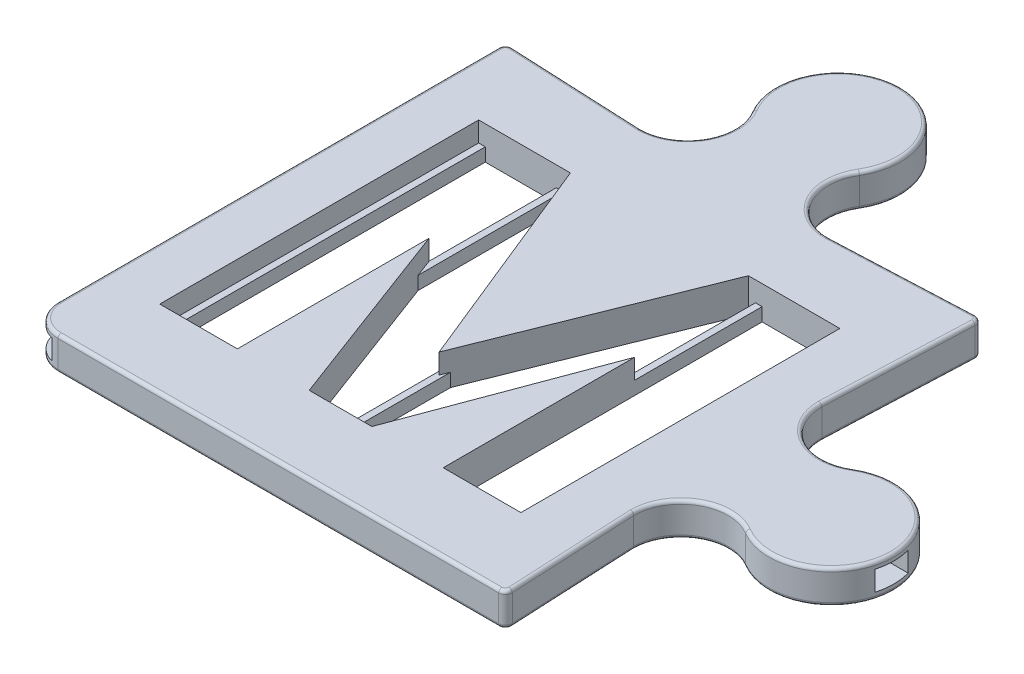
SolidWorks part; units mm, degrees
ref_plane "Front Plane" through (0, 0, 0) normal (0, 0, 1) x (1, 0, 0)
ref_plane "Top Plane" through (0, 0, 0) normal (0, 1, 0) x (1, 0, 0)
ref_plane "Right Plane" through (0, 0, 0) normal (1, 0, 0) x (0, 0, -1)
sketch "Sketch1" plane through (0, 0, 0) normal (0, 1, 0) x (1, 0, 0)
  line L0 (-31, -36) -> (37, -36) construction
  line L1 (-36, 37) -> (-36, -31) construction
  line L2 (-14.1421, 36) -> (-36, 37) construction
  line L3 (37, 37) -> (14.1421, 36) construction
  line L4 (36, 13.1421) -> (37, 37) construction
  line L5 (37, -36) -> (36, -15.1421) construction
  line L6 (-35.4, 36.3719) -> (-35.4, -31)
  line L7 (-36, 36) -> (36, 36) construction
  line L8 (-36, 36) -> (-36, -36) construction
  line L9 (-36, -36) -> (36, -36) construction
  line L10 (36, 36) -> (36, -36) construction
  line L11 (-31, -35.4) -> (36.3705, -35.4)
  line L12 (36.3705, -35.4) -> (35.4, -15.1568)
  line L13 (35.4, 13.155) -> (36.3732, 36.372)
  line L14 (36.3732, 36.372) -> (14.1555, 35.4)
  line L15 (-14.1562, 35.4) -> (-35.4, 36.3719)
  line L16 (-30, -24) -> (30, -24) construction
  line L17 (-30, 29) -> (30, 29) construction
  line L18 (-30, 29) -> (-30, -31) construction
  line L19 (-30, -31) -> (30, -31) construction
  line L20 (30, 29) -> (30, -31) construction
  line L21 (-30, 24) -> (30, 24) construction
  line L22 (-30, 24) -> (-30, -26) construction
  line L23 (-30, -26) -> (30, -26) construction
  line L24 (30, 24) -> (30, -26) construction
  arc A0 (-36, -31) -> (-31, -36) centre (-31, -31) ccw construction
  arc A1 (-14.1421, 36) -> (-8.571, 45.8485) centre (-14.1421, 42.5) ccw construction
  arc A2 (8.571, 45.8485) -> (-8.571, 45.8485) centre (0, 51) ccw construction
  arc A3 (8.571, 45.8485) -> (14.1421, 36) centre (14.1421, 42.5) ccw construction
  arc A4 (36, 13.1421) -> (45.8485, 7.571) centre (42.5, 13.1421) ccw construction
  arc A5 (45.8485, -9.571) -> (45.8485, 7.571) centre (51, -1) ccw construction
  arc A6 (45.8485, -9.571) -> (36, -15.1421) centre (42.5, -15.1421) ccw construction
  arc A7 (-35.4, -31) -> (-31, -35.4) centre (-31, -31) ccw
  arc A8 (46.1576, -9.0567) -> (35.4, -15.1568) centre (42.5, -15.1421) ccw
  arc A9 (46.1576, -9.0567) -> (46.1576, 7.0567) centre (51, -1) ccw
  arc A10 (35.4, 13.155) -> (46.1576, 7.0567) centre (42.5, 13.1421) ccw
  arc A11 (8.0567, 46.1576) -> (14.1555, 35.4) centre (14.1421, 42.5) ccw
  arc A12 (8.0567, 46.1576) -> (-8.0567, 46.1576) centre (0, 51) ccw
  arc A13 (-14.1562, 35.4) -> (-8.0567, 46.1576) centre (-14.1421, 42.5) ccw
  point P32 (36, 0)
  point P34 (0, 36)
  dimension "D5" = 6.5
  dimension "D6" = 10
  dimension "D7" = 6.5
  dimension "D13" = 5
  dimension "D9" = 10
  dimension "D11" = 6.5
  dimension "D12" = 6.5
  dimension "D1" = 72
  dimension "D2" = 1
  dimension "D3" = 1
  dimension "D4" = 15
  dimension "D8" = 1
  dimension "D10" = 35
  dimension "D14" = 15
  dimension "D15" = 36
  dimension "D16" = 1
  dimension "D18" = 60
  dimension "D19" = 60
  dimension "D20" = 5
  dimension "D21" = 6
  dimension "D22" = 5
  dimension "D23" = 50
  dimension "D24" = 2
  dimension "D17" = 0.6
extrude "Boss-Extrude1" add sketch "Sketch1" along normal blind 5
sketch "Sketch6" plane through (0, 0, 0) normal (0, -1, 0) x (1, 0, 0)
  line L0 (-35.4, -36.3719) -> (-35.4, 31) construction
  line L1 (-35.4, 17.9) -> (-27.4, 17.9)
  line L2 (-35.4, 17.9) -> (-35.4, -16.1)
  line L3 (-35.4, -16.1) -> (-27.4, -16.1)
  line L4 (-27.4, 17.9) -> (-27.4, -16.1)
  line L5 (-31, 35.4) -> (36.3705, 35.4) construction
  line L6 (-35.4, 14.65) -> (-30.4, 14.65)
  line L7 (-35.4, 14.65) -> (-35.4, -12.85)
  line L8 (-35.4, -12.85) -> (-30.4, -12.85)
  line L9 (-30.4, 14.65) -> (-30.4, -12.85)
  point P15 (-27.4, 0.9)
  point P16 (-30.4, 0.9)
  line M28 (-35.4, 31) -> (-35.4, -36.3719)
  dimension "D1" = 8
  dimension "D2" = 20.75
  dimension "D3" = 27.5
  dimension "D4" = 5
  dimension "D5" = 34
extrude "Cut-Extrude3" cut sketch "Sketch6" against normal blind 3 from offset 1 contours L6 L9 L8 L3 L4 L1 M28 | L9 L6 L2 L8 region at (-29.8665, 0, 0.9) region at (-32.9, 0, 0.9) offset against normal yes
extrude "Cut-Extrude4" cut sketch "Sketch6<3>" against normal up to next contours L9 L6 L2 L8 region at (-32.9, 0, 0.9)
sketch "Sketch6<3>" plane through (0, 0, 0) normal (0, -1, 0) x (1, 0, 0) same geometry as "Sketch6"
sketch "Sketch8" plane through (0, 0, 0) normal (0, -1, 0) x (1, 0, 0)
  line L1 (-2.5, -51.4) -> (2.5, -51.4)
  line L2 (-2.5, -51.4) -> (-2.5, -60.4)
  line L3 (-2.5, -60.4) -> (2.5, -60.4)
  line L4 (2.5, -51.4) -> (2.5, -60.4)
  line L5 (51.4, 3.5) -> (60.4, 3.5)
  line L6 (51.4, 3.5) -> (51.4, -1.5)
  line L7 (51.4, -1.5) -> (60.4, -1.5)
  line L8 (60.4, 3.5) -> (60.4, -1.5)
  arc A0 (-8.0567, -46.1576) -> (8.0567, -46.1576) centre (0, -51) ccw construction
  arc A1 (46.1576, -7.0567) -> (46.1576, 9.0567) centre (51, 1) ccw construction
  point P4 (0, -60.4)
  point P13 (60.4, 1)
  dimension "D1" = 5
  dimension "D2" = 9
  dimension "D3" = 5
  dimension "D4" = 9
extrude "Cut-Extrude5" cut sketch "Sketch8" against normal blind 3 from offset 1 offset against normal yes
sketch "Sketch9" plane through (0, 0, 0) normal (0, -1, 0) x (1, 0, 0)
  line L0 (-31, 35.4) -> (36.3705, 35.4) construction
  line L1 (-35.4, 14.65) -> (-35.4, 31) construction
  line L2 (-31.7636, 35.3332) -> (-35.4, 31) construction
  line L3 (-33.2571, 29.735) -> (-30.0429, 33.565) construction
  line L4 (-30.0429, 33.565) -> (-33.2571, 29.735) construction
  line L5 (-30.0429, 33.565) -> (-32.7119, 35.8048)
  line L6 (-33.2571, 29.735) -> (-35.926, 31.9747)
  line L7 (-32.7119, 35.8048) -> (-35.926, 31.9747)
  circle A0 centre (-31.65, 31.65) radius 2.5
  arc A1 (-31, 35.4) -> (-35.4, 31) centre (-31, 31) ccw construction
  arc M41 (-31, 35.4) -> (-35.4, 31) centre (-31, 31) ccw
  dimension "D1" = 5
  dimension "D3" = 3.75
  dimension "D4" = 5.6569
  dimension "D2" = 3.75
extrude "Cut-Extrude6" cut sketch "Sketch9" against normal blind 3 from offset 1 contours A0 L5 L6 M41 | A0 L5 region at (-33.6239, 0, 33.3064) region at (-31.65, 0, 31.65) offset against normal yes
sketch "Sketch11" plane through (-35.4, 0, 0) normal (-1, 0, 0) x (0, 0, 1)
  line L0 (-13.155, 0) -> (-36.372, 0) construction
  line L1 (-25.1, 3) -> (-19.1, 3)
  line L2 (-25.1, 3) -> (-25.1, 1.5)
  line L3 (-25.1, 1.5) -> (-19.1, 1.5)
  line L4 (-19.1, 3) -> (-19.1, 1.5)
  line L5 (-16.1, 4) -> (-16.1, 1) construction
  line L6 (35.4, 0) -> (15.1568, 0) construction
  line L7 (20.9, 3) -> (26.9, 3)
  line L8 (20.9, 3) -> (20.9, 1.5)
  line L9 (20.9, 1.5) -> (26.9, 1.5)
  line L10 (26.9, 3) -> (26.9, 1.5)
  line L12 (17.9, 4) -> (17.9, 1) construction
  dimension "D1" = 3
  dimension "D2" = 1.5
  dimension "D3" = 3
  dimension "D4" = 6
  dimension "D5" = 3
  dimension "D6" = 1.5
  dimension "D7" = 6
  dimension "D8" = 3
fillet "Fillet1" radius 0.5 17 edges at (-35.4, 0, 22.825) (-34.1113, 0, 34.1113) (2.6853, 0, 35.4) (35.8853, 0, 25.2784) (38.9978, 0, 8.966) (60.4, 0, 1) (38.9986, 0, -6.9655) (35.8866, 0, -24.7635) (25.2643, 0, -35.886) (7.9657, 0, -38.9984) (0, 0, -60.4) (-7.9658, 0, -38.9981) (-24.7781, 0, -35.886) (-35.4, 0, -24.611) (-32.9, 0, -12.85) (-30.4, 0, 0.9) (-32.9, 0, 14.65)
fillet "Fillet2" radius 0.5 13 edges at (-7.9658, 5, -38.9981) (0, 5, -60.4) (7.9657, 5, -38.9984) (25.2643, 5, -35.886) (35.8866, 5, -24.7635) (38.9986, 5, -6.9655) (60.4, 5, 1) (38.9978, 5, 8.966) (35.8853, 5, 25.2784) (2.6853, 5, 35.4) (-34.1113, 5, 34.1113) (-35.4, 5, -2.686) (-24.7781, 5, -35.886)
fillet "Fillet3" radius 1 9 edges at (36.2202, 0.1464, -36.2187) (36.2202, 4.8536, -36.2187) (36.3732, 2.5, -36.372) (-35.2536, 0.1464, -36.2186) (-35.2536, 4.8536, -36.2186) (36.2169, 0.1464, 35.2536) (36.2169, 4.8536, 35.2536) (36.3705, 2.5, 35.4) (-35.4, 2.5, -36.3719)
extrude "Cut-Extrude9" cut sketch "Sketch11" against normal blind 3
chamfer "Chamfer1" distance 1 angle 50 2 edges at (-35.4, 1.5, 23.9) (-35.4, 1.5, -22.1) first distance on face at (-35.4, 2.25, -22.1)
sketch "Sketch12" plane through (0, 5, 0) normal (0, 1, 0) x (1, 0, 0)
  text T0 "M" font "Poppins" height 48
extrude "Cut-Extrude10" cut sketch "Sketch12" against normal through all
sketch "Sketch13" plane through (0, 0, 0) normal (0, -1, 0) x (1, 0, 0)
  line L0 (-27.3401, -24.2477) -> (-13.5297, -24.2477) construction
  line L1 (-15.6567, -24.2477) -> (-14.6567, -24.2477)
  line L2 (-15.6567, -24.2477) -> (-15.6567, -2.4363)
  line L3 (-15.6567, -2.4363) -> (-14.6567, -2.4363)
  line L4 (-14.6567, -24.2477) -> (-14.6567, -2.4363)
  line L5 (-4.8438, 23.7523) -> (-15.6567, -5.1051) construction
  line L6 (13.27, -24.2477) -> (27.021, -24.2477) construction
  line L7 (15.3277, -24.2477) -> (14.3277, -24.2477)
  line L8 (15.3277, -24.2477) -> (15.3277, -2.3563)
  line L9 (15.3277, -2.3563) -> (14.3277, -2.3563)
  line L10 (14.3277, -24.2477) -> (14.3277, -2.3563)
  line L11 (15.3277, -5.0358) -> (4.5841, 23.7523) construction
  line L12 (-13.5297, -24.2477) -> (-0.0656, 8.9823) construction
  line L13 (-0.568, 7.7423) -> (0.432, 7.7423)
  line L14 (-0.568, 7.7423) -> (-0.568, 23.7523)
  line L15 (-0.568, 23.7523) -> (0.432, 23.7523)
  line L16 (0.432, 7.7423) -> (0.432, 23.7523)
  line L17 (4.5841, 23.7523) -> (-4.8438, 23.7523) construction
  line L18 (-0.0656, 8.9823) -> (13.27, -24.2477) construction
  line L19 (15.3277, 23.7523) -> (15.3277, -5.0358) construction
  line L20 (-15.6567, -5.1051) -> (-15.6567, 23.7523) construction
  line L22 (-27.3401, 23.7523) -> (-26.3401, 23.7523)
  line L23 (-27.3401, 23.7523) -> (-27.3401, -24.2477)
  line L24 (-27.3401, -24.2477) -> (-26.3401, -24.2477)
  line L25 (-26.3401, 23.7523) -> (-26.3401, -24.2477)
  line L26 (27.021, 23.7523) -> (26.021, 23.7523)
  line L27 (27.021, 23.7523) -> (27.021, -24.2477)
  line L28 (27.021, -24.2477) -> (26.021, -24.2477)
  line L29 (26.021, 23.7523) -> (26.021, -24.2477)
  dimension "D1" = 1
  dimension "D2" = 1
  dimension "D3" = 1
  dimension "D4" = 1
  dimension "D5" = 1
extrude "Boss-Extrude2" add sketch "Sketch13" against normal blind 2
